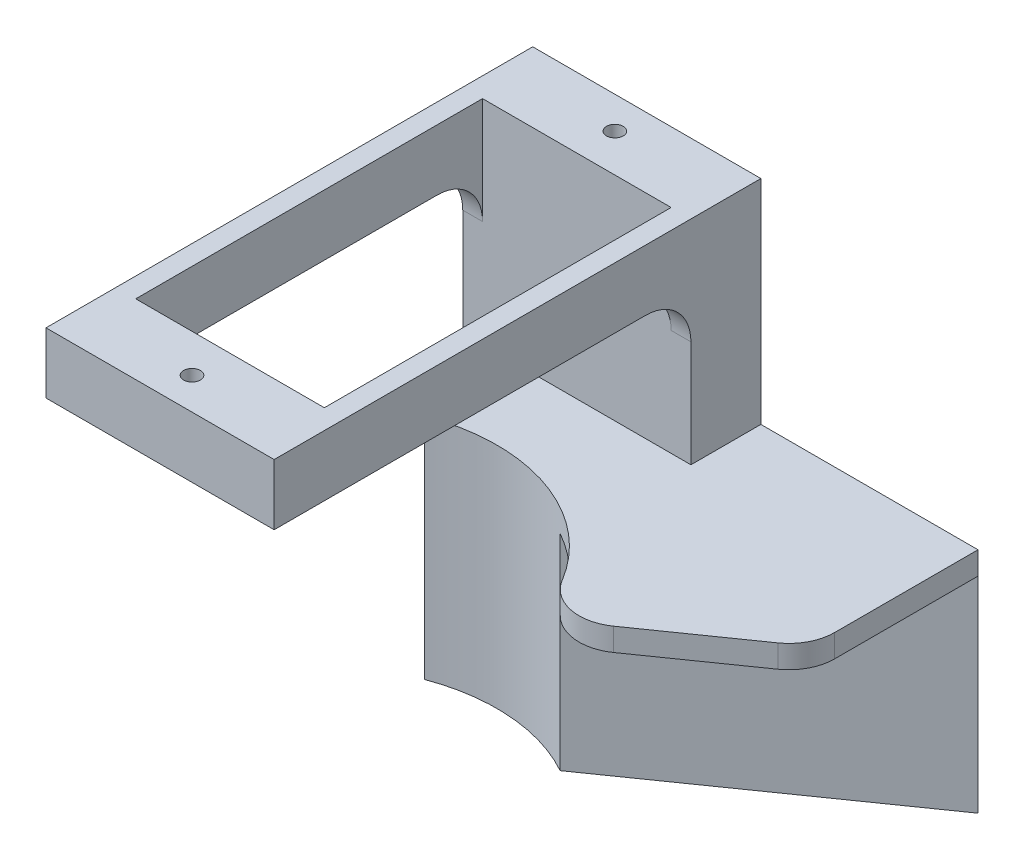
SolidWorks part; units mm, degrees
ref_plane "Front Plane" through (0, 0, 0) normal (0, 0, 1) x (1, 0, 0)
ref_plane "Top Plane" through (0, 0, 0) normal (0, 1, 0) x (1, 0, 0)
ref_plane "Right Plane" through (0, 0, 0) normal (1, 0, 0) x (0, 0, -1)
sketch "Sketch1" plane through (0, 0, 0) normal (0, 0, 1) x (1, 0, 0)
  line L0 (0, 13.9) -> (0, -13.9) construction
  line L1 (-6.2, 11.4) -> (6.2, 11.4)
  line L2 (-6.2, 11.4) -> (-6.2, -11.4)
  line L3 (-6.2, -11.4) -> (6.2, -11.4)
  line L4 (6.2, 11.4) -> (6.2, -11.4)
  line L5 (-6.2, 11.4) -> (6.2, -11.4) construction
  line L6 (-6.2, -11.4) -> (6.2, 11.4) construction
  line L8 (-7.5, 16) -> (7.5, 16)
  line L9 (-7.5, 16) -> (-7.5, -16)
  line L10 (-7.5, -16) -> (7.5, -16)
  line L11 (7.5, 16) -> (7.5, -16)
  line L12 (-7.5, 16) -> (7.5, -16) construction
  line L13 (-7.5, -16) -> (7.5, 16) construction
  circle A0 centre (0, 13.9) radius 0.55
  circle A1 centre (0, -13.9) radius 0.55
  point P0 (0, 0)
  point P5 (0, 13.9)
  point P6 (0, -13.9)
  point P10 (0, 0)
  dimension "D4" = 1.1
  dimension "D5" = 1.1
  dimension "D1" = 22.8
  dimension "D2" = 12.4
  dimension "D3" = 27.8
  dimension "D6" = 32
  dimension "D7" = 15
extrude "Servo Mount Plate" add sketch "Sketch1" along normal blind 4
sketch "Sketch3" plane through (0, 0, 4) normal (0, 0, 1) x (1, 0, 0)
  line L0 (-6.2, -11.4) -> (6.2, -11.4) construction
  line L1 (-6.2, -11.4) -> (6.2, -11.4)
  line L2 (7.5, -16) -> (7.5, 16) construction
  line L3 (-7.5, -16) -> (7.5, -16)
  line L4 (-7.5, -16) -> (-7.5, -11.4)
  line L5 (-7.5, -11.4) -> (7.5, -11.4)
  line L6 (7.5, -16) -> (7.5, -11.4)
  point P9 (7.5, -11.7747)
  line M3 (7.5, -16) -> (7.5, 16)
  line M5 (-7.5, 16) -> (-7.5, -16)
  line M6 (-7.5, -16) -> (7.5, -16)
  line M9 (6.2, -11.4) -> (-6.2, -11.4)
  circle M11 centre (0, -13.9) radius 0.55
extrude "Boss-Extrude3" add sketch "Sketch3" along normal blind 25 contours L5 M5 M6 M3 M9 M11 | M11 region at (0, -11.5569, 4) region at (0, -13.9, 4)
ref_plane "Outer Surface" through (0, 0, 29) normal (0, 0, 1) x (1, 0, 0)
ref_plane "Inner Surface" through (0, 0, 14) normal (0, 0, 1) x (1, 0, 0)
sketch "Sketch5" plane through (0, 0, 14) normal (0, 0, 1) x (1, 0, 0)
  line L0 (-7.5, -11.4) -> (7.5, -11.4) construction
  line L1 (-7.5, -11.4) -> (7.5, -11.4) construction
  line L2 (-11.3511, 7.1943) -> (21.7737, -16)
  line L3 (-6.5377, 14.8109) -> (21.7737, -5.013)
  line L4 (-4.0447, -5.4152) -> (-7.5, -11.4)
  line L5 (-7.5, -16) -> (7.5, -16) construction
  line L6 (-7.5, -16) -> (7.5, -16) construction
  line L7 (21.7737, -5.013) -> (21.7737, -16)
  line L8 (21.7737, -16) -> (7.5, -16)
  line L9 (7.5, -16) -> (7.5, -6.0054)
  line L10 (7.5, -11.4) -> (7.5, 16) construction
  line L13 (-7.5, -11.4) -> (7.5, -11.4)
  circle A1 centre (0, 5.35) radius 11.5
  point P0 (0, 0)
  point P15 (-1.5753, -5.7554)
  dimension "D1" = 16.75
  dimension "D2" = 23
  dimension "D3" = 35
  dimension "D4" = 5
  dimension "D5" = 9
  dimension "D6" = 60
extrude "Boss-Extrude9" add sketch "Sketch5" along normal up to surface (15 mm away) contours A1 L2 L7 L3 | L9 L8 L2 | A1 L13 L9 L2 region at (15.226, -6.3122, 14) region at (0.9045, -8.6548, 14) region at (12.2579, -12.6685, 14) up to face at (0, -13.7, 29)
extrude "Cut-Extrude3" cut sketch "Sketch5<8>" against normal blind 13.5 from surface contours A1 L2 L7 L3 region at (15.226, -6.3122, 14) starting at face at (6.2295, -9.1268, 29)
sketch "Sketch5<8>" plane through (0, 0, 14) normal (0, 0, 1) x (1, 0, 0) same geometry as "Sketch5"
fillet "Fillet1" radius 3 4 edges at (11.1263, 2.4423, 14.75) (6.85, -11.4, 4) (-6.85, -11.4, 4) (21.7737, -5.013, 14.75)
move or copy body "Body-Move/Copy1" bodies to move or copy 112 copy no rotation origin (0, 0, 14.5) rotation axis (1, 0, 0) rotation angle 90
